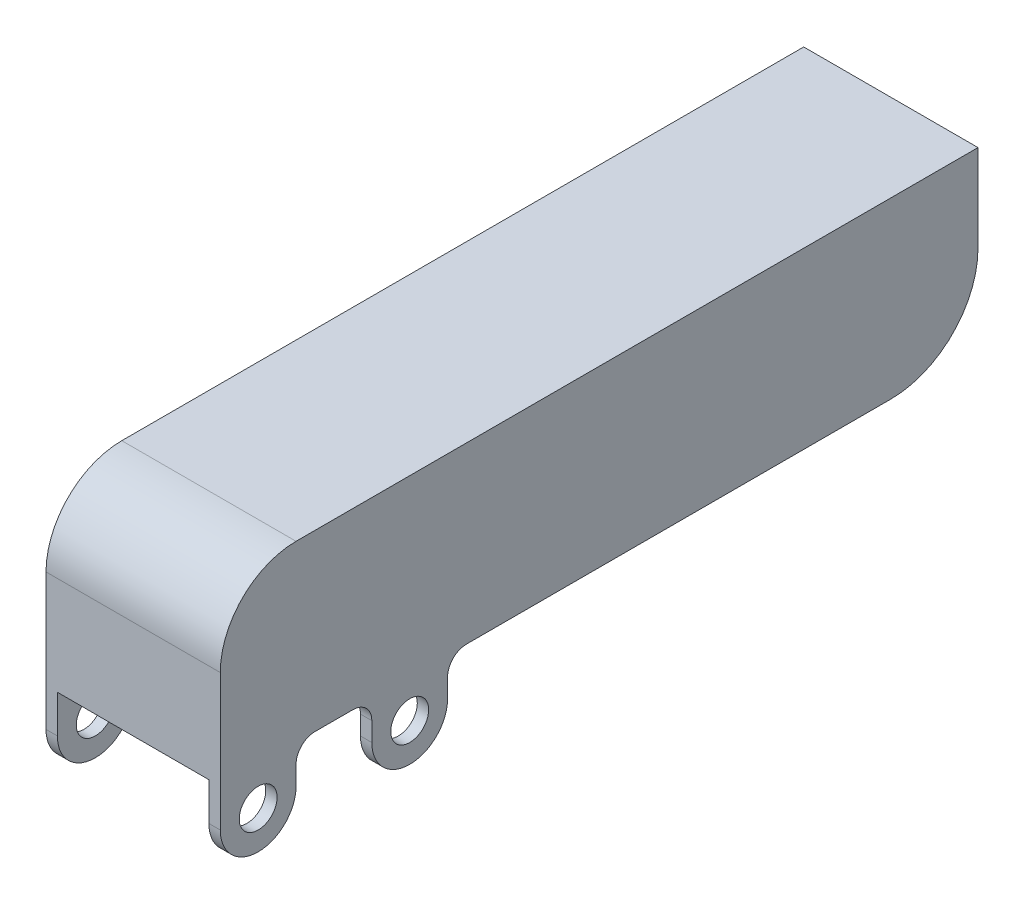
SolidWorks part; units mm, degrees
ref_plane "Front Plane" through (0, 0, 0) normal (0, 0, 1) x (1, 0, 0)
ref_plane "Top Plane" through (0, 0, 0) normal (0, 1, 0) x (1, 0, 0)
ref_plane "Right Plane" through (0, 0, 0) normal (1, 0, 0) x (0, 0, -1)
sketch "Profile Sketch" plane through (0, 0, 0) normal (1, 0, 0) x (0, 0, -1)
  line L1 (-80, 23) -> (100, 23)
  line L2 (-100, 3) -> (-100, -23)
  line L3 (-100, -23) -> (77, -23)
  line L4 (100, 23) -> (100, 0)
  line L5 (-100, 23) -> (100, -23) construction
  line L6 (-100, -23) -> (100, 23) construction
  arc A0 (-100, 3) -> (-80, 23) centre (-80, 3) cw
  arc A1 (77, -23) -> (100, 0) centre (77, 0) ccw
  point P0 (0, 0)
  dimension "D3" = 20
  dimension "D4" = 23
  dimension "D1" = 200
  dimension "D2" = 46
extrude "Profile Extrude" add sketch "Profile Sketch" along normal blind 23 and the other way blind 23
shell "Profile Shell" thickness 3 removed face at (0, -23, 11.5) removed face at (0, -13.8817, -90.8817) removed face at (0, 11.5, -100)
sketch "Cuff Joint Pin Sketch" plane through (23, 0, 0) normal (1, 0, 0) x (0, 0, -1)
  circle A0 centre (77, 0) radius 7.5
  arc A1 (77, -23) -> (100, 0) centre (77, 0) ccw construction
  dimension "D1" = 15
extrude "Cuff Join Pin Extrude" add sketch "Cuff Joint Pin Sketch" against normal up to surface (43 mm away) up to face at (-20, -0.7071, -0.7071)
sketch "Hydraulic Arm Holes Sketch" plane through (23, 0, 0) normal (1, 0, 0) x (0, 0, -1)
  line L0 (-100, -23) -> (-100, -33)
  line L1 (-80, -23) -> (-80, -33)
  line L2 (-100, -23) -> (77, -23) construction
  line L3 (-100, -33) -> (-80, -33) construction
  line L4 (-100, -23) -> (-80, -23)
  line L6 (-60, -33) -> (-40, -33) construction
  line L7 (-60, -33) -> (-60, -23)
  line L8 (-60, -23) -> (-40, -23)
  line L9 (-40, -23) -> (-40, -33)
  arc A0 (-100, -33) -> (-80, -33) centre (-90, -33) ccw
  arc A1 (-60, -33) -> (-40, -33) centre (-50, -33) ccw
  circle A2 centre (-90, -33) radius 5
  circle A3 centre (-50, -33) radius 5
  dimension "D1" = 10
  dimension "D3" = 10
  dimension "D6" = 10
  dimension "D7" = 10
  dimension "D2" = 10
  dimension "D4" = 10
  dimension "D5" = 20
extrude "Hydraulic Arm Holes Extrude 1" add sketch "Hydraulic Arm Holes Sketch" against normal up to surface (3 mm away) up to face at (20, 0, -84.5)
extrude "Hydraulic Arm Holes Extrude 2" add sketch "Hydraulic Arm Holes Sketch<2>" against normal up to surface (46 mm away) from surface up to face at (-23, 0.3964, 0.3964) starting at face at (-20, 0, -84.5)
sketch "Hydraulic Arm Holes Sketch<2>" plane through (23, 0, 0) normal (1, 0, 0) x (0, 0, -1) same geometry as "Hydraulic Arm Holes Sketch"
fillet "Holes Tabs Fillet" radius 5 6 edges at (21.5, -23, 40) (-21.5, -23, 40) (-21.5, -23, 60) (-21.5, -23, 80) (21.5, -23, 60) (21.5, -23, 80)
